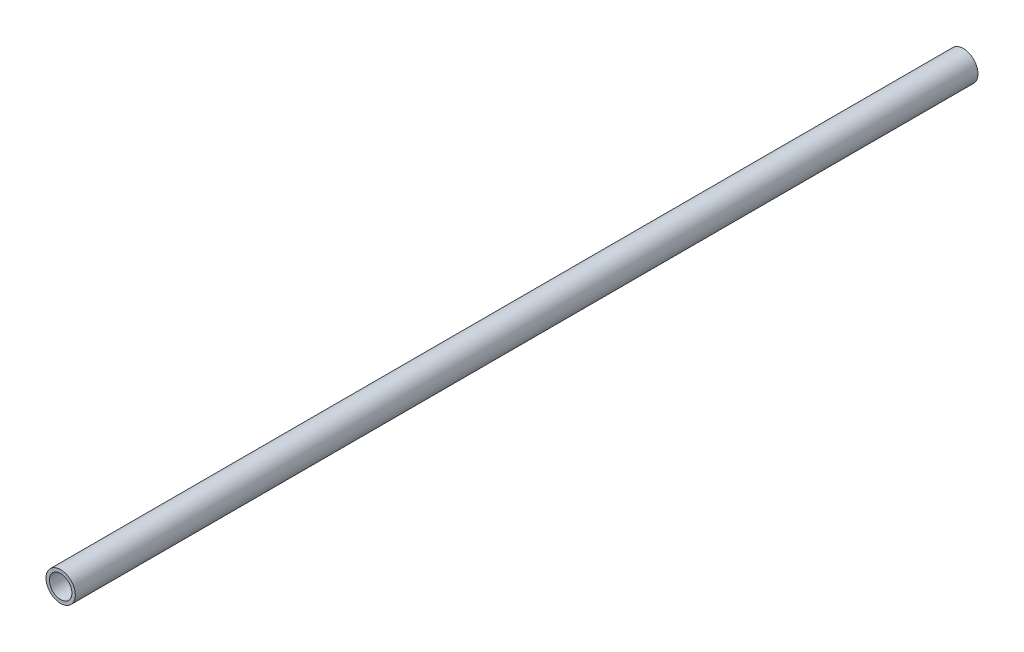
SolidWorks part; units mm, degrees
material "6061 Alloy"
ref_plane "Front Plane" through (0, 0, 0) normal (0, 0, 1) x (1, 0, 0)
ref_plane "Top Plane" through (0, 0, 0) normal (0, 1, 0) x (1, 0, 0)
ref_plane "Right Plane" through (0, 0, 0) normal (1, 0, 0) x (0, 0, -1)
sketch "Sketch1" plane through (0, 0, 0) normal (0, 0, 1) x (1, 0, 0)
  circle A0 centre (390.7614, 31.0815) radius 6.5
  circle A1 centre (390.7614, 31.0815) radius 5
extrude "Boss-Extrude1" add sketch "Sketch1" along normal blind 400
